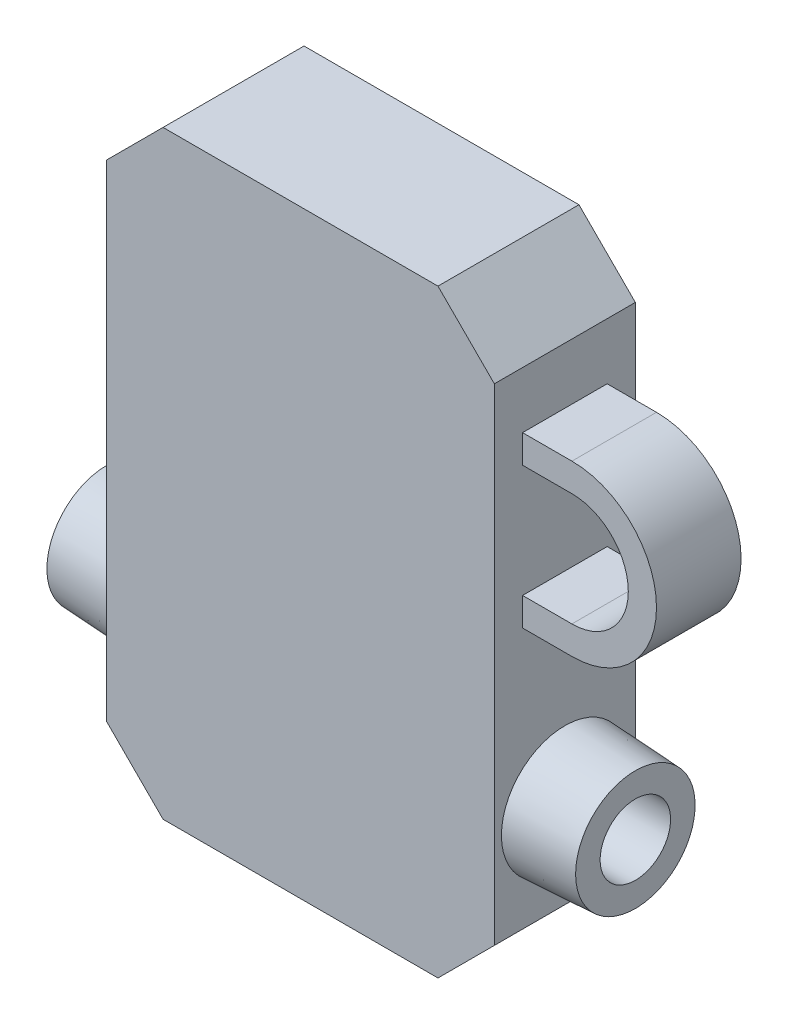
SolidWorks part; units mm, degrees
note: '?' marks a value the reader was unsure of.
material "PEI"
ref_plane "前视基准面" through (0, 0, 0) normal (0, 0, 1) x (1, 0, 0)
ref_plane "上视基准面" through (0, 0, 0) normal (0, 1, 0) x (1, 0, 0)
ref_plane "右视基准面" through (0, 0, 0) normal (1, 0, 0) x (0, 0, -1)
other "Configuration Table"
sketch "草图1" plane through (0, 0, 0) normal (0, 0, 1) x (1, 0, 0)
  line L0 (0, 38.5) -> (4, 42.5)
  line L1 (4, 0) -> (23.5, 0)
  line L2 (0, 4) -> (0, 38.5)
  line L3 (4, 42.5) -> (23.5, 42.5)
  line L4 (27.5, 4) -> (27.5, 38.5)
  line L5 (23.5, 42.5) -> (27.5, 38.5)
  line L6 (23.5, 0) -> (27.5, 4)
  line L7 (4, 0) -> (0, 4)
  point P0 (0, 0)
  point P1 (27.5, 42.5)
  point P2 (0, 42.5)
  point P3 (27.5, 0)
  dimension "D1" = 27.5
  dimension "D2" = 42.5
extrude "凸台-拉伸1" add sketch "草图1" along normal blind 10
sketch "草图2" plane through (0, 0, 0) normal (-1, 0, 0) x (0, 0, 1)
  line L0 (10, 38.5) -> (10, 4) construction
  line L1 (10, 0) -> (0, 0) construction
  circle A0 centre (5, 10.5) radius 4.5
  circle A1 centre (5, 10.5) radius 2.5
  dimension "D1" = 9
  dimension "D4" = 5
  dimension "D2" = 5
  dimension "D3" = 10.5
extrude "凸台-拉伸2" add sketch "草图2" along normal blind 5 and the other way offset from surface (32.5 mm away) 5 contours A0 A1 other way up to face at (27.5, 21.25, 5)
draft "拔模1" type of draft neutral plane draft angle 3 faces to draft 1 face at (32.5, 10.5, 9.5) neutral plane through (27.5, 4, 10) neutral plane normal (1, 0, 0) parameters "D1"=3
draft "拔模2" type of draft neutral plane draft angle 3 faces to draft 1 face at (-5, 10.5, 9.5) neutral plane through (0, 4, 10) neutral plane normal (-1, 0, 0) parameters "D1"=3
ref_plane "基准面1" through (0, 0, 5) normal (0, 0, 1) x (1, 0, 0)
sketch "草图3" plane through (0, 0, 5) normal (0, 0, 1) x (1, 0, 0)
  line L0 (31, 32.5) -> (27.5, 32.5)
  line L1 (27.5, 4) -> (27.5, 38.5) construction
  line L2 (27.5, 32.5) -> (27.5, 24.5)
  line L3 (27.5, 24.5) -> (31, 24.5)
  line L4 (31, 34.5) -> (25.5, 34.5)
  line L5 (25.5, 34.5) -> (25.5, 22.5)
  line L6 (25.5, 22.5) -> (31, 22.5)
  line L7 (23.5, 42.5) -> (4, 42.5) construction
  line L8 (0, 38.5) -> (0, 4) construction
  arc A0 (31, 24.5) -> (31, 32.5) centre (31, 28.5) ccw
  arc A1 (31, 22.5) -> (31, 34.5) centre (31, 28.5) ccw
  point P16 (37, 28.5)
  dimension "D2" = 10
  dimension "D3" = 20
  dimension "D4" = 37
  dimension "D1" = 2
extrude "凸台-拉伸3" add sketch "草图3" along normal blind 3 and the other way blind 3
other "连接点1" parameters "直径"=4, "端头长度"=6
ref_axis "基准轴1" through (-15, 10.5, 5) along (1, 0, 0)?
other "连接点2" parameters "直径"=4, "端头长度"=6
ref_axis "基准轴2" through (42.5, 10.5, 5) along (-1, 0, 0)?
